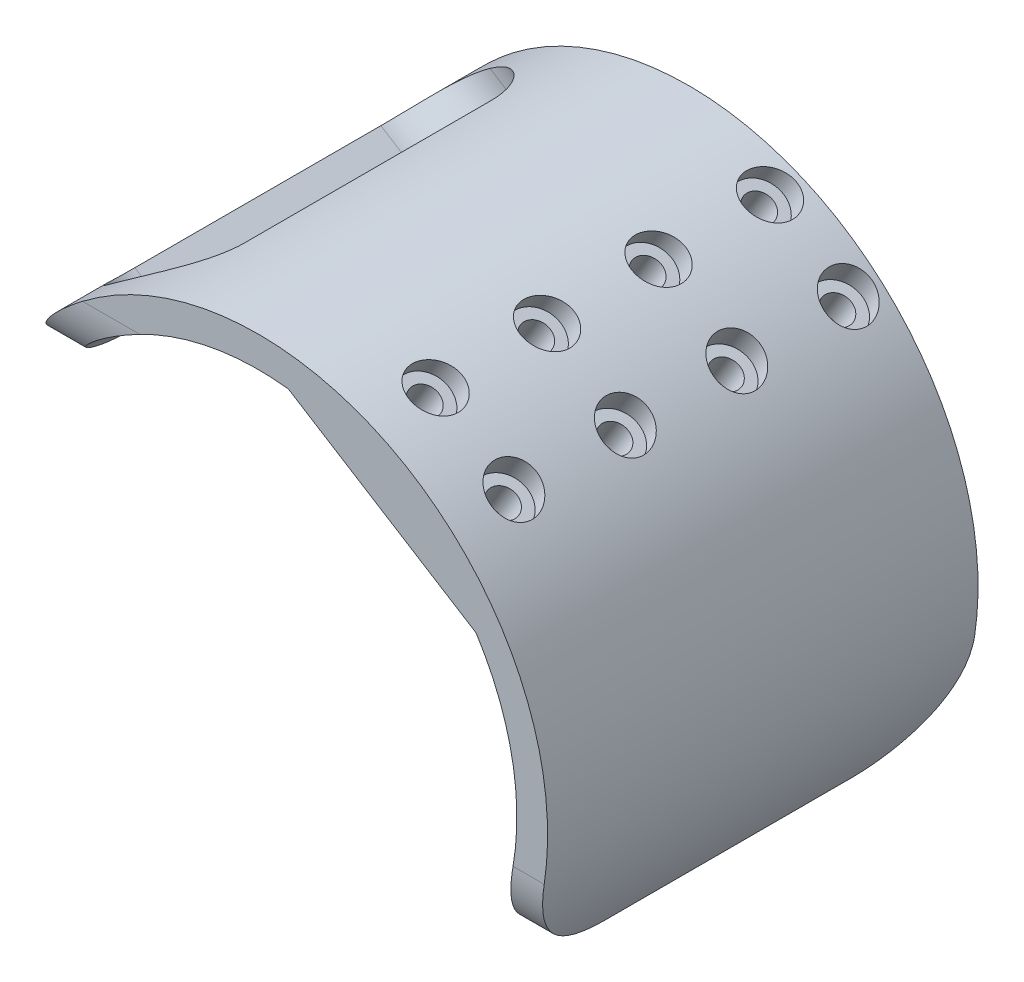
SolidWorks part; units mm, degrees
ref_plane "Plan de face" through (0, 0, 0) normal (0, 0, 1) x (1, 0, 0)
ref_plane "Plan de dessus" through (0, 0, 0) normal (0, 1, 0) x (1, 0, 0)
ref_plane "Plan de droite" through (0, 0, 0) normal (1, 0, 0) x (0, 0, -1)
sketch "Esquisse2" plane through (0, 0, 15) normal (0, 0, 1) x (1, 0, 0)
  line L0 (-73.5002, 11.2174) -> (-67.7143, 11.2174)
  line L1 (3.5979, -33.3527) -> (9.3691, -33.3527)
  line L2 (-27.235, 30.6113) -> (3.2925, 11.5317)
  line L3 (-44.7779, -3.1178) -> (-37.2727, -7.8086) construction
  line L4 (-26.8437, -14.3267) -> (-19.3384, -19.0175) construction
  line L5 (-27.235, 30.6113) -> (3.2925, 11.5317)
  line L6 (-27.235, 30.6113) -> (-25.0898, 34.0436)
  line L7 (3.2925, 11.5317) -> (5.4377, 14.9639)
  line L8 (-25.0898, 34.0436) -> (5.4377, 14.9639)
  arc A0 (3.5979, -33.3527) -> (-67.7143, 11.2174) centre (-32.1112, -11.1524) ccw
  arc A1 (9.3691, -33.3527) -> (-73.5002, 11.2174) centre (-32.1112, -11.1524) ccw
  dimension "D1" = 5
  dimension "D2" = 0
  dimension "D3" = 0
extrude "Boss.-Extru.1" add sketch "Esquisse2" along normal blind 70 from surface contours L1 A1 L0 A0 | L5 L6 L8 L7
sketch "Esquisse3" plane through (6.1076, 9.7722, 0) normal (-0.53, -0.848, 0) x (0.848, -0.53, 0)
  circle A0 centre (-28.8193, -110.625) radius 2.3
  circle A1 centre (-13.8196, -110.625) radius 2.3
  circle A2 centre (-13.8196, -128.75) radius 2.3
  circle A3 centre (-28.8193, -146.875) radius 2.3
  circle A4 centre (-28.8193, -128.75) radius 2.3
  circle A5 centre (-13.8196, -146.875) radius 2.3
  circle A6 centre (-13.8196, -165) radius 2.3
  circle A7 centre (-28.8193, -165) radius 2.3
  dimension "D1" = 4.6
extrude "Enlèv. mat.-Extru.1" cut sketch "Esquisse3" against normal through all
sketch "Esquisse4" plane through (6.1076, 9.7722, 0) normal (-0.53, -0.848, 0) x (0.848, -0.53, 0)
  circle A1 centre (-13.8196, -110.625) radius 4
  circle A2 centre (-13.8196, -128.75) radius 4
  circle A3 centre (-13.8196, -146.875) radius 4
  circle A4 centre (-13.8196, -165) radius 4
  circle A5 centre (-28.8193, -165) radius 4
  circle A6 centre (-28.8193, -146.875) radius 4
  circle A7 centre (-28.8193, -128.75) radius 4
  circle A8 centre (-28.8193, -110.625) radius 4
  dimension "D1" = 8
extrude "Enlèv. mat.-Extru.3" cut sketch "Esquisse4" along normal blind 4 from offset 9 offset against normal yes
sketch "Esquisse5" plane through (-30.7986, 19.2491, 0) normal (-0.848, 0.53, 0) x (0, 0, 1)
  line L0 (-165, 1.5239) -> (-105, 1.5239)
  line L1 (-165, 1.5239) -> (-165, -18.4761)
  line L2 (-105, 1.5239) -> (-105, -18.4761)
  line L3 (-165, -18.4761) -> (-105, -18.4761)
  line L4 (-168, 11.5239) -> (-17, 11.5239) construction
  line L5 (-170, 20.5713) -> (-170, -29.4427) construction
  dimension "D1" = 10
  dimension "D2" = 30
  dimension "D3" = 60
  dimension "D4" = 5
extrude "Enlèv. mat.-Extru.4" cut sketch "Esquisse5" along normal blind 50
fillet "Congé1" radius 10 4 edges at (-46.6022, 30.9234, -105) (-46.6022, 30.9234, -165) (-65.0312, 18.8566, -105) (-65.0312, 18.8566, -165)
fillet "Congé2" radius 15 4 edges at (-70.6073, 11.2174, -170) (-70.6073, 11.2174, -100) (6.4835, -33.3527, -170) (6.4835, -33.3527, -100)
